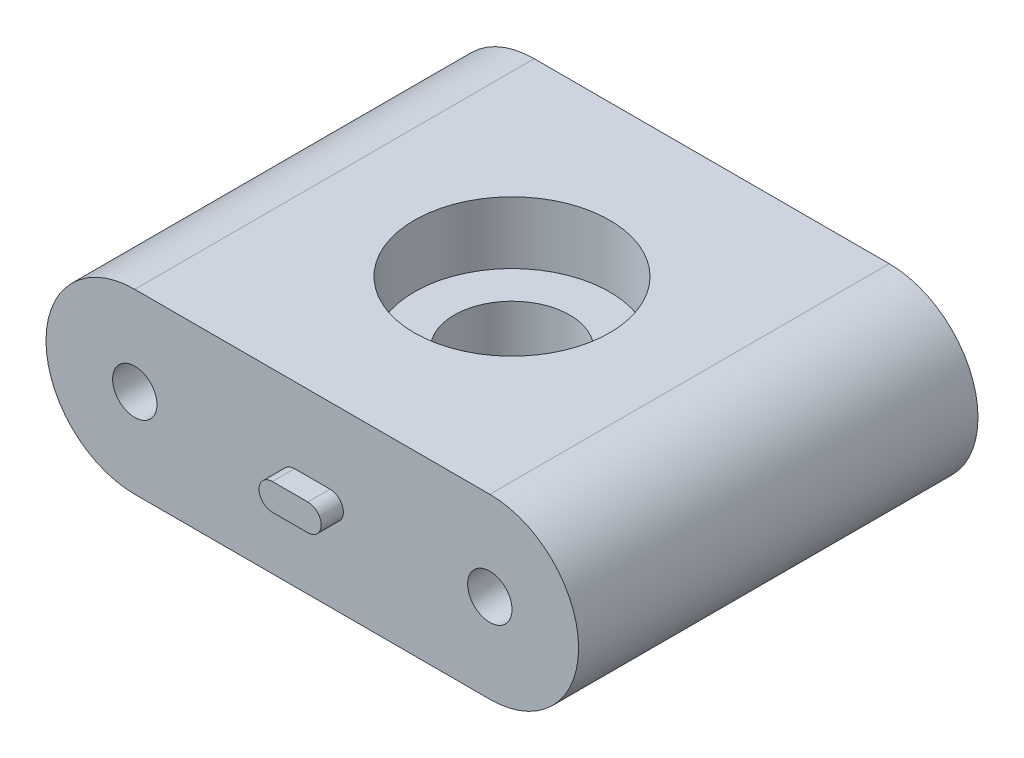
SolidWorks part; units mm, degrees
ref_plane "Front Plane" through (0, 0, 0) normal (0, 0, 1) x (1, 0, 0)
ref_plane "Top Plane" through (0, 0, 0) normal (0, 1, 0) x (1, 0, 0)
ref_plane "Right Plane" through (0, 0, 0) normal (1, 0, 0) x (0, 0, -1)
sketch "Sketch1" plane through (0, 0, 0) normal (0, 0, 1) x (1, 0, 0)
  line L0 (-4, 0) -> (4, 0) construction
  line L1 (-4, 2) -> (4, 2)
  line L2 (-4, -2) -> (4, -2)
  line L3 (-0.4, 0) -> (0.4, 0) construction
  line L4 (-0.4, 0.3) -> (0.4, 0.3)
  line L5 (-0.4, -0.3) -> (0.4, -0.3)
  arc A0 (-4, 2) -> (-4, -2) centre (-4, 0) ccw
  arc A1 (4, -2) -> (4, 2) centre (4, 0) ccw
  circle A2 centre (-4, 0) radius 0.5
  circle A3 centre (4, 0) radius 0.5
  arc A4 (-0.4, 0.3) -> (-0.4, -0.3) centre (-0.4, 0) ccw
  arc A5 (0.4, -0.3) -> (0.4, 0.3) centre (0.4, 0) ccw
  point P3 (0, 0)
  point P14 (0, 0)
  dimension "D2" = 1
  dimension "D3" = 2
  dimension "D1" = 8
  dimension "D4" = 0.8
  dimension "D5" = 0.6
extrude "Boss-Extrude1" add sketch "Sketch1" along normal mid plane 9
extrude "Boss-Extrude2" add sketch "Sketch1<2>" along normal mid plane 10 contours L4 A5 L5 A4
sketch "Sketch1<2>" plane through (0, 0, 0) normal (0, 0, 1) x (1, 0, 0) same geometry as "Sketch1"
sketch "Sketch2" plane through (0, 2, 0) normal (0, 1, 0) x (1, 0, 0)
  point P0 (0, 0)
hole_wizard "CBORE for M2 Cheese Head Screw1" positions "Sketch2" profile "Sketch3" counterbore size "M2" standard "ISO" end condition through all
sketch "Sketch3" plane through (0, 2, 0) normal (1, 0, 0) x (0, 0, 1)
  line L0 (0, 0) -> (0, 4)
  line L1 (0, 4) -> (1.3, 4)
  line L3 (1.3, 4) -> (1.3, 1.4)
  line L4 (1.3, 1.4) -> (2.2, 1.4)
  line L5 (2.2, 1.4) -> (2.2, 0)
  line L7 (2.2, 0) -> (0, 0)
  line L11 (0, -6.35) -> (0, 107.95) construction
  dimension "Thru Hole Dia." = 2.6
  dimension "Thru Hole Depth" = 4
  dimension "C'Bore Dia." = 4.4
  dimension "C'Bore Depth" = 1.4
